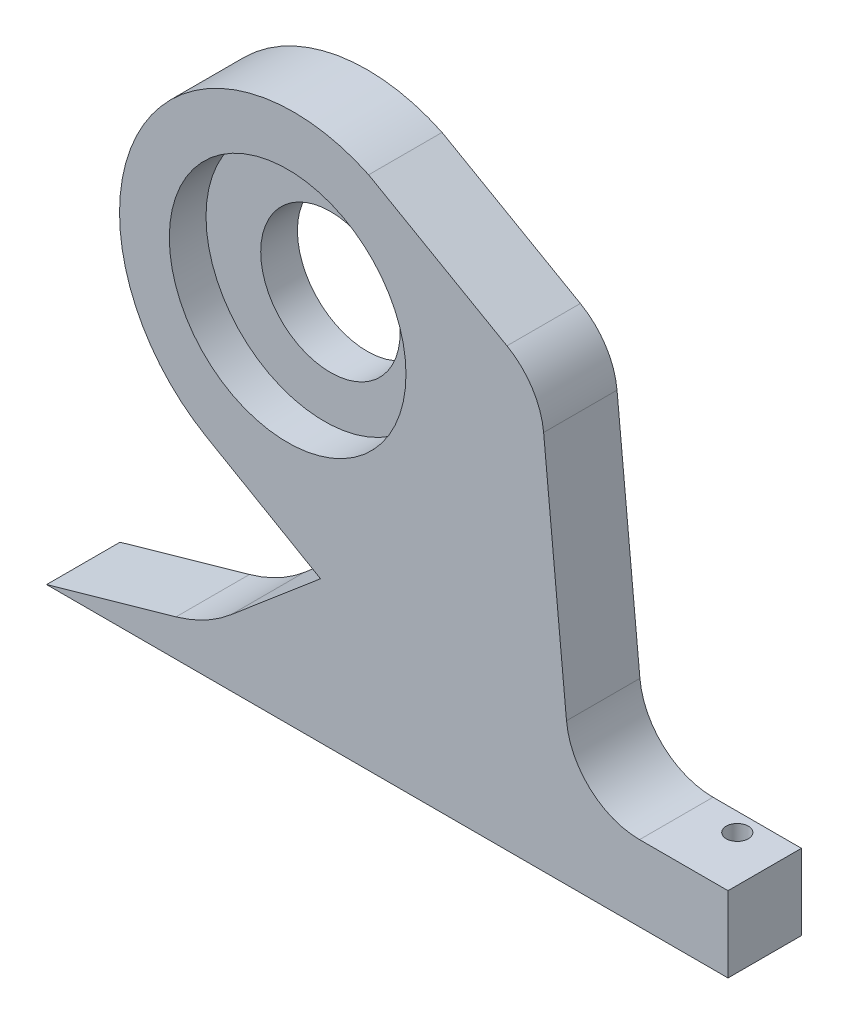
SolidWorks part; units mm, degrees
ref_plane "Front Plane" through (0, 0, 0) normal (0, 0, 1) x (1, 0, 0)
ref_plane "Top Plane" through (0, 0, 0) normal (0, 1, 0) x (1, 0, 0)
ref_plane "Right Plane" through (0, 0, 0) normal (1, 0, 0) x (0, 0, -1)
sketch "Sketch1" plane through (0, 0, 0) normal (0, 0, 1) x (1, 0, 0)
  line L0 (21.2946, 15.4992) -> (22.7802, 0.0334)
  line L2 (-2.5397, 33.9855) -> (16.2995, 23.2268)
  line L3 (22.7802, 0.0334) -> (24.4112, -16.9452)
  line L4 (34.3653, -25.989) -> (46.4112, -25.989)
  line L5 (-24.6077, -7.9899) -> (-9.0967, -16.9452)
  line L7 (46.4112, -25.989) -> (46.4112, -36.2909)
  line L8 (46.4112, -36.2909) -> (24.4112, -36.2909)
  line L9 (24.4112, -36.2909) -> (-46.4112, -36.2909)
  line L10 (-9.0967, -16.9452) -> (-21.306, -27.2953)
  line L11 (-28.7712, -31.2775) -> (-46.4112, -36.2909)
  arc A0 (-24.6077, -7.9899) -> (-2.5397, 33.9855) centre (-12.7427, 12.5609) cw
  arc A1 (24.4112, -16.9452) -> (34.3653, -25.989) centre (34.3653, -15.989) ccw
  arc A2 (21.2946, 15.4992) -> (16.2995, 23.2268) centre (11.3404, 14.543) ccw
  arc A3 (-21.306, -27.2953) -> (-28.7712, -31.2775) centre (-34.2388, -12.0394) cw
  dimension "D1" = 10
  dimension "D2" = 10
  dimension "D3" = 22
  dimension "D4" = 10.3019
  dimension "D5" = 12.0458
extrude "Boss-Extrude1" add sketch "Sketch1" along normal blind 10
sketch "Sketch4" plane through (0, 0, 10) normal (0, 0, 1) x (1, 0, 0)
  circle A0 centre (-13.5737, 12.9978) radius 16.12
  dimension "D1" = 32.24
  dimension "D2" = 23.7114
extrude "Cut-Extrude1" cut sketch "Sketch4" against normal blind 5 contours A0
sketch "Sketch5" plane through (0, -25.989, 0) normal (0, 1, 0) x (1, 0, 0)
  line L0 (46.4112, -10) -> (34.3653, -10) construction
  circle A0 centre (40.1734, -2.5) radius 1.5
  point P6 (40.3882, -10)
  dimension "D1" = 3
  dimension "D2" = 7.5
extrude "Cut-Extrude2" cut sketch "Sketch5" against normal up to surface (10.3019 mm away) up to face at (0, -36.2909, 5)
sketch "Sketch6" plane through (0, 0, 0) normal (0, 0, -1) x (-1, 0, 0)
  circle A2 centre (12.7427, 12.5609) radius 9.5
  dimension "D1" = 19
extrude "Cut-Extrude3" cut sketch "Sketch6" against normal up to surface (5 mm away) up to face at (2.5463, 12.9978, 5)
